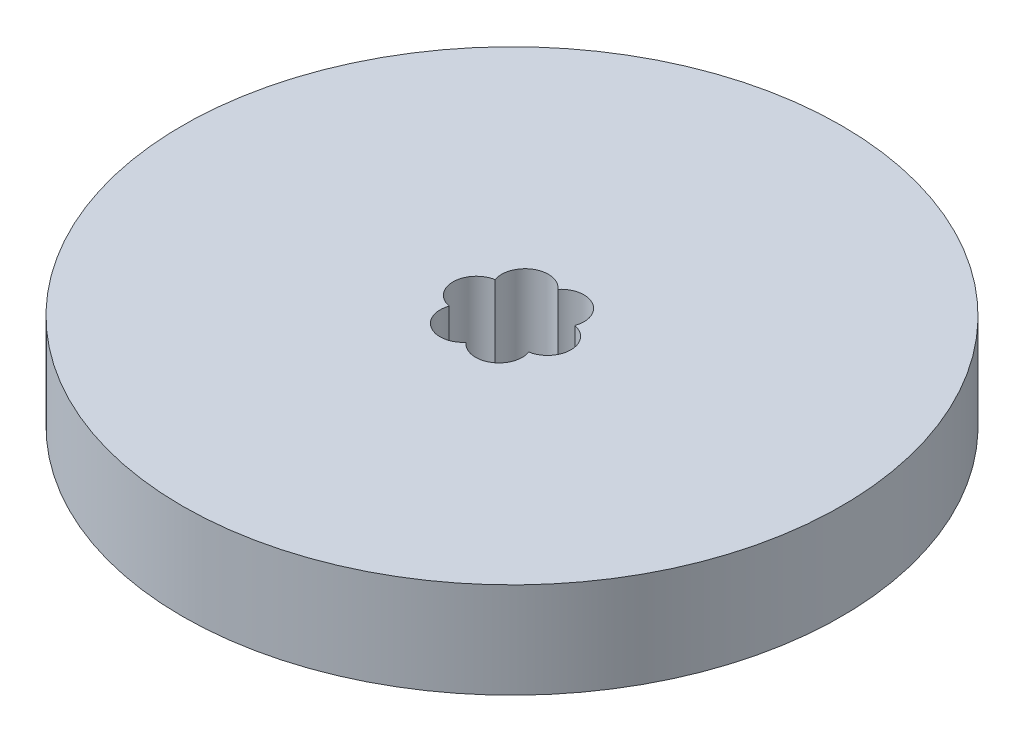
SolidWorks part; units mm, degrees
ref_plane "Front Plane" through (0, 0, 0) normal (0, 0, 1) x (1, 0, 0)
ref_plane "Top Plane" through (0, 0, 0) normal (0, 1, 0) x (1, 0, 0)
ref_plane "Right Plane" through (0, 0, 0) normal (1, 0, 0) x (0, 0, -1)
sketch "Sketch1" plane through (0, 0, 0) normal (0, 1, 0) x (1, 0, 0)
  circle A0 centre (0, 0) radius 100
  dimension "FLANGE_OD" = 200
extrude "Boss-Extrude1" add sketch "Sketch1" along normal blind 29
sketch "Sketch2" plane through (0, 0, 0) normal (0, 1, 0) x (1, 0, 0)
  circle A0 centre (0, 0) radius 12.5
  dimension "BORE_D" = 25
extrude "Cut-Extrude1" cut sketch "Sketch2" along normal through all
sketch "Sketch3" plane through (0, 29, 0) normal (0, 1, 0) x (1, 0, 0)
  circle A0 centre (0, 0) radius 10.7947 construction
  circle A1 centre (-10.7947, 0) radius 7.0896
  dimension "BOLT_D" = 14.1793
  dimension "BOLT_PCD" = 21.5893
extrude "Cut-Extrude2" cut sketch "Sketch3" against normal blind 24.6087
pattern_circular "CirPattern1" count 6 over 360 about axis through (0, 0, 0) along (0, 1, 0) of "Cut-Extrude2"
